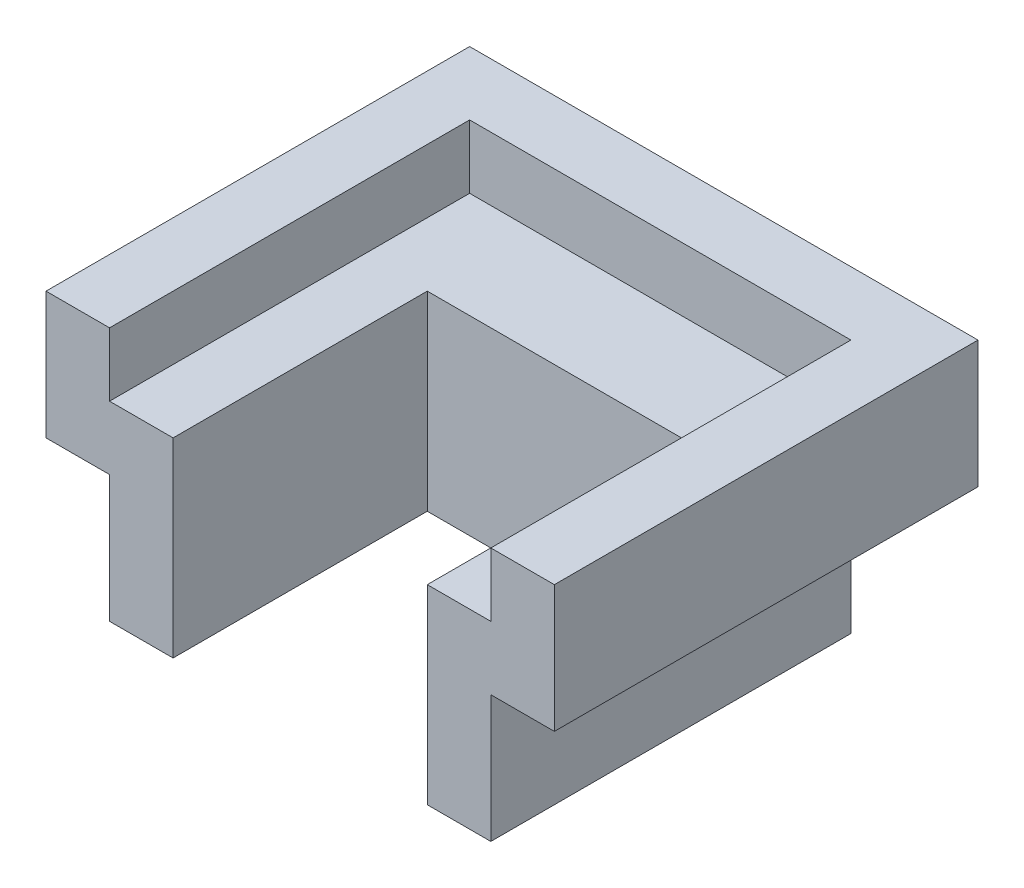
SolidWorks part; units mm, degrees
ref_plane "Front Plane" through (0, 0, 0) normal (0, 0, 1) x (1, 0, 0)
ref_plane "Top Plane" through (0, 0, 0) normal (0, 1, 0) x (1, 0, 0)
ref_plane "Right Plane" through (0, 0, 0) normal (1, 0, 0) x (0, 0, -1)
sketch "Sketch1" plane through (0, 0, 0) normal (0, 1, 0) x (1, 0, 0)
  line L0 (-38.1, 0) -> (38.1, 0)
  line L1 (-38.1, 0) -> (-38.1, -63.5)
  line L2 (-38.1, -63.5) -> (-19.05, -63.5)
  line L3 (-19.05, -63.5) -> (-19.05, -25.4)
  line L4 (-19.05, -25.4) -> (19.05, -25.4)
  line L5 (19.05, -25.4) -> (19.05, -63.5)
  line L6 (19.05, -63.5) -> (38.1, -63.5)
  line L7 (38.1, -63.5) -> (38.1, 0)
  line L8 (-28.575, -63.5) -> (-28.575, -9.525)
  line L9 (-28.575, -9.525) -> (28.575, -9.525)
  line L10 (28.575, -9.525) -> (28.575, -63.5)
  point P11 (0, 0)
  dimension "D1" = 76.2
  dimension "D2" = 63.5
  dimension "D3" = 19.05
  dimension "D4" = 38.1
  dimension "D5" = 53.975
  dimension "D6" = 57.15
extrude "Boss-Extrude1" add sketch "Sketch1" along normal mid plane 19.05 contours L9 L10 L6 L7 L0 L1 L2 L8 region at (0, 0, 0.9919)
extrude "Boss-Extrude2" add sketch "Sketch1<3>" against normal blind 28.575 contours L10 L9 L8 L2 L3 L4 L5 L6 region at (-27.7889, 0, 36.5125)
sketch "Sketch1<3>" plane through (0, 0, 0) normal (0, 1, 0) x (1, 0, 0) same geometry as "Sketch1"
